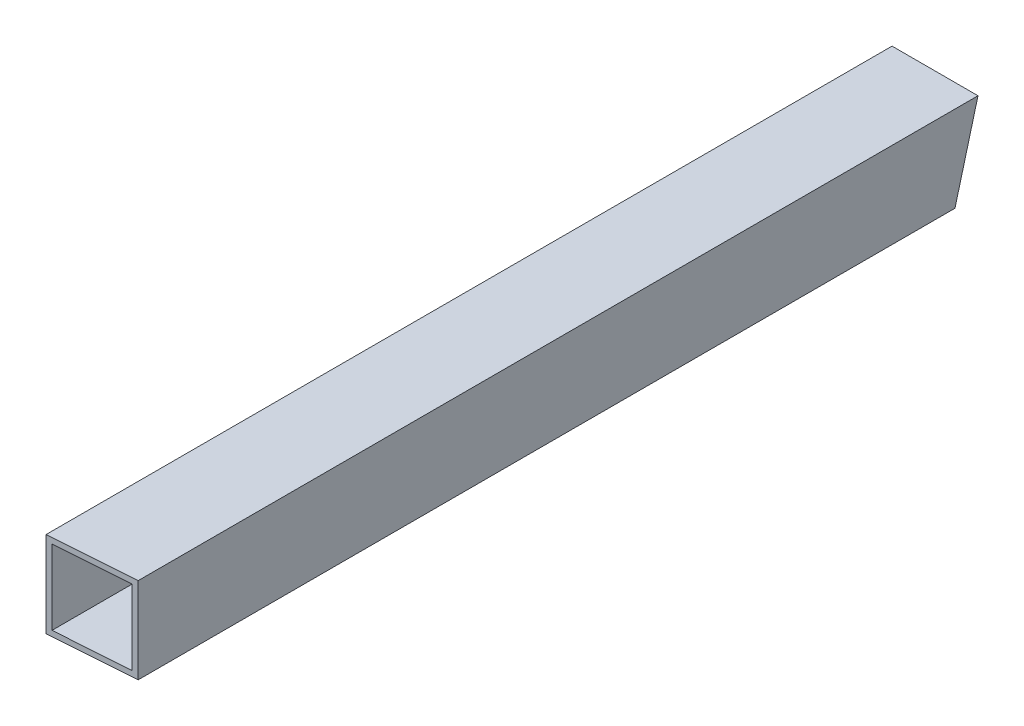
SolidWorks part; units mm, degrees
ref_plane "Front Plane" through (0, 0, 0) normal (0, 0, 1) x (1, 0, 0)
ref_plane "Top Plane" through (0, 0, 0) normal (0, 1, 0) x (1, 0, 0)
ref_plane "Right Plane" through (0, 0, 0) normal (1, 0, 0) x (0, 0, -1)
sketch "Sketch6" plane through (0, 0, 0) normal (0, 0, 1) x (1, 0, 0)
  line L1 (0, 0) -> (25.4, 0)
  line L2 (0, 0) -> (0, -25.4)
  line L3 (0, -25.4) -> (25.4, -25.4)
  line L4 (25.4, 0) -> (25.4, -25.4)
  dimension "D1" = 25.4
  dimension "D2" = 25.4
extrude "Boss-Extrude1" add sketch "Sketch6" along normal blind 250
sketch "Sketch7" plane through (0, 0, 0) normal (0, 1, 0) x (1, 0, 0)
  line L0 (0, -250) -> (25.4, -248.1806)
  line L1 (25.4, -250) -> (25.4, 0) construction
  line L3 (25.4, -248.1806) -> (25.4, -250)
  line L4 (0, -250) -> (0, 0) construction
  line L5 (25.4, -250) -> (0, -250)
  dimension "D1" = 85.903
extrude "Cut-Extrude2" cut sketch "Sketch7" against normal through all
shell "Shell1" thickness 1.651 removed face at (12.7, -12.7, 249.0903) removed face at (12.7, -12.7, 0)
sketch "Sketch9" plane through (0, 0, 0) normal (-1, 0, 0) x (0, 0, 1)
  line L0 (0, 0) -> (6.8059, -25.4)
  line L1 (250, -25.4) -> (0, -25.4) construction
  line L2 (6.8059, -25.4) -> (0, -25.4)
  line L3 (0, -25.4) -> (0, 0)
  dimension "D1" = 15
extrude "Cut-Extrude3" cut sketch "Sketch9" against normal through all
equation "\"A\"=250"
equation "\"t1len\"=250"
equation "\"D1@Boss-Extrude1\"=\"t1len\""
equation "\"D1@Sketch7\"= ( 180 - atn ( 36 / 250 ) ) / 2"
